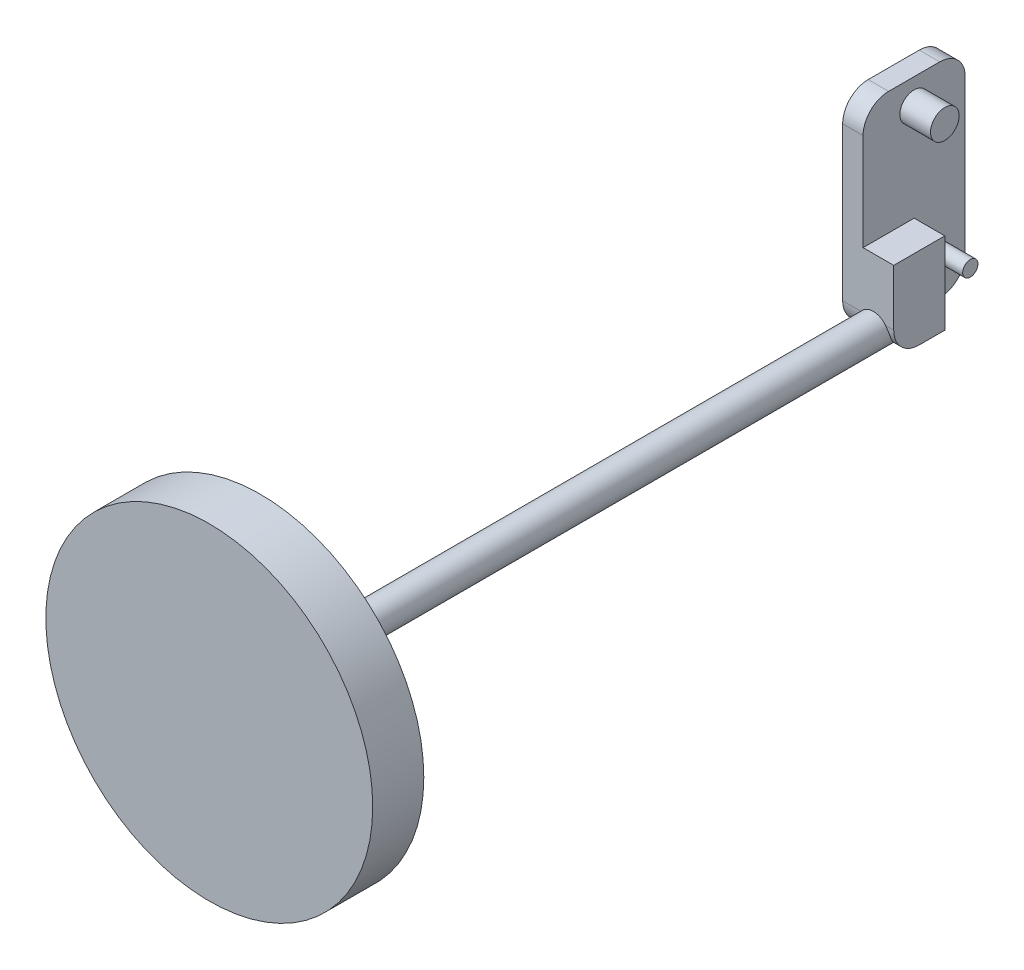
SolidWorks part; units mm, degrees
ref_plane "Front Plane" through (0, 0, 0) normal (0, 0, 1) x (1, 0, 0)
ref_plane "Top Plane" through (0, 0, 0) normal (0, 1, 0) x (1, 0, 0)
ref_plane "Right Plane" through (0, 0, 0) normal (1, 0, 0) x (0, 0, -1)
sketch "Sketch1" plane through (0, 0, 0) normal (0, 0, 1) x (1, 0, 0)
  circle A0 centre (0, 0) radius 400
  dimension "D1" = 800
extrude "Boss-Extrude1" add sketch "Sketch1" along normal blind 125
sketch "Sketch2" plane through (0, 0, 0) normal (0, 0, -1) x (-1, 0, 0)
  circle A0 centre (0, 0) radius 37.5
  dimension "D1" = 75
extrude "Boss-Extrude2" add sketch "Sketch2" along normal blind 1500
sketch "Sketch3" plane through (0, 0, -1500) normal (0, 0, -1) x (-1, 0, 0)
  line L1 (75, 460) -> (25, 460)
  line L2 (75, 460) -> (75, -40)
  line L3 (75, -40) -> (25, -40)
  line L4 (25, 460) -> (25, -40)
  dimension "D1" = 500
  dimension "D2" = 50
  dimension "D3" = 460
  dimension "D4" = 25
extrude "Boss-Extrude3" add sketch "Sketch3" along normal blind 250
sketch "Sketch4" plane through (-25, 0, 0) normal (-1, 0, 0) x (0, 0, 1)
  line L0 (-1500, -40) -> (-1500, 460) construction
  line L1 (-1500, -40) -> (-1625, -40)
  line L2 (-1500, -40) -> (-1500, 160)
  line L3 (-1500, 160) -> (-1625, 160)
  line L4 (-1625, -40) -> (-1625, 160)
  line L5 (-1750, -40) -> (-1500, -40) construction
  circle A0 centre (-1687.5, 60) radius 18.75
  circle A1 centre (-1625, 397.09) radius 35
  dimension "D5" = 37.5
  dimension "D6" = 70
  dimension "D1" = 125
  dimension "D2" = 200
  dimension "D3" = 62.5
  dimension "D4" = 100
  dimension "D7" = 397.09
extrude "Boss-Extrude4" add sketch "Sketch4" against normal blind 75
fillet "Fillet1" radius 62.5 4 edges at (-12.5, -40, -1500) (-50, -40, -1750) (-50, 460, -1750) (-50, 460, -1500)
